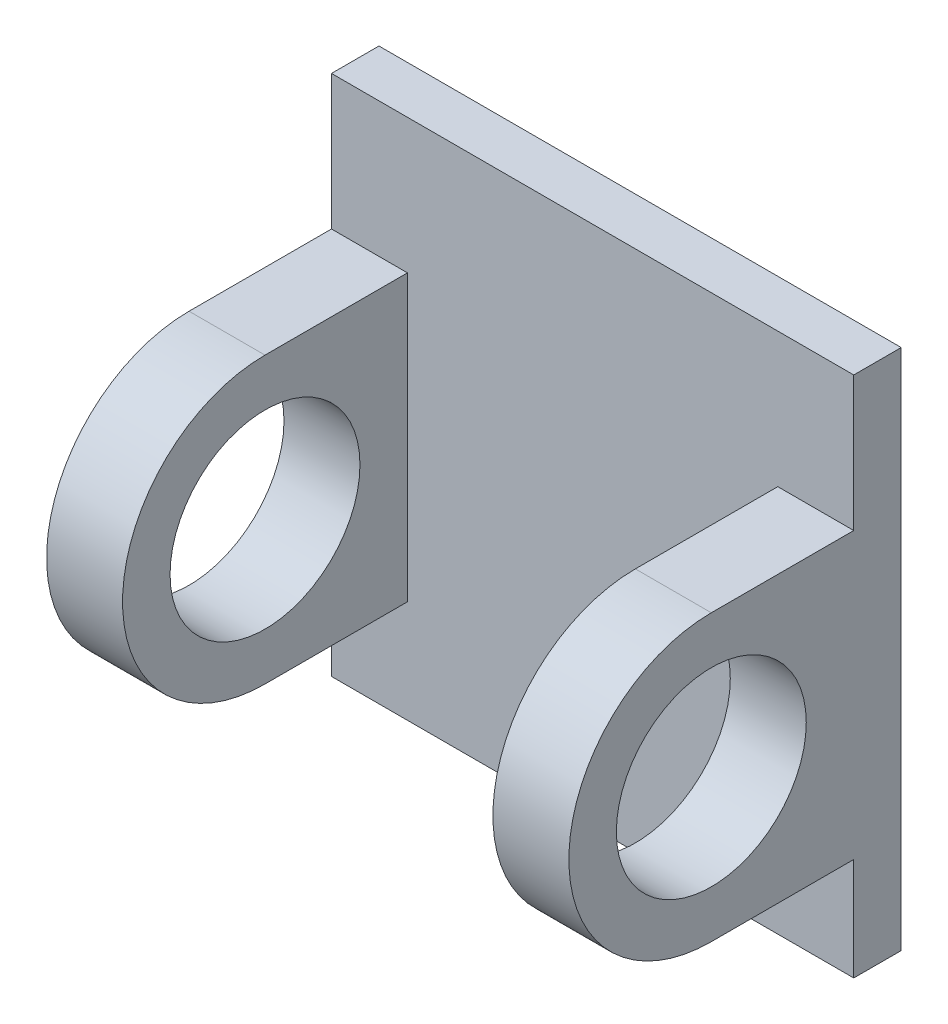
SolidWorks part; units mm, degrees
material "PLA"
ref_plane "Front Plane" through (0, 0, 0) normal (1, 0, 0) x (0, 1, 0)
ref_plane "Top Plane" through (0, 0, 0) normal (0, 0, 1) x (0, 1, 0)
ref_plane "Right Plane" through (0, 0, 0) normal (0, 1, 0) x (-1, 0, 0)
sketch "Sketch1" plane through (0, 0, 0) normal (0, 0, 1) x (0, 1, 0)
  line L1 (-13.75, -13.75) -> (13.75, -13.75)
  line L2 (-13.75, -13.75) -> (-13.75, 13.75)
  line L3 (-13.75, 13.75) -> (13.75, 13.75)
  line L4 (13.75, -13.75) -> (13.75, 13.75)
  line L5 (-13.75, -13.75) -> (13.75, 13.75) construction
  line L6 (-13.75, 13.75) -> (13.75, -13.75) construction
  point P0 (0, 0)
  dimension "D1" = 27.5
extrude "Boss-Extrude1" add sketch "Sketch1" along normal blind 2.5
sketch "Sketch2" plane through (13.75, 0, 0) normal (1, 0, 0) x (0, 1, 0)
  line L0 (-8.3445, 2.5) -> (6.6555, 2.5)
  line L1 (-13.75, 2.5) -> (13.75, 2.5) construction
  line L2 (6.6555, 2.5) -> (6.6555, 10)
  line L3 (-8.3445, 2.5) -> (-8.3445, 10)
  arc A0 (6.6555, 10) -> (-8.3445, 10) centre (-0.8445, 10) ccw
  circle A1 centre (-0.8445, 10) radius 5
  point P5 (-0.8445, 2.5)
  dimension "D1" = 10
  dimension "D2" = 2.5
  dimension "D3" = 7.5
extrude "Boss-Extrude2" add sketch "Sketch2" against normal blind 27.5
sketch "Sketch3" plane through (0, 0, 0) normal (1, 0, 0) x (0, 1, 0)
  line L1 (-13.75, 2.5) -> (13.75, 2.5)
  line L2 (-13.75, 2.5) -> (-13.75, 18.2629)
  line L3 (-13.75, 18.2629) -> (13.75, 18.2629)
  line L4 (13.75, 2.5) -> (13.75, 18.2629)
extrude "Cut-Extrude1" cut sketch "Sketch3" against normal offset from surface 4 and the other way offset from surface 4 up to face at (-13.75, -0.4223, 4.6875) other way up to face at (13.75, -0.4223, 4.6875)
sketch "Sketch4" plane through (0, 13.75, 0) normal (0, 1, 0) x (-1, 0, 0)
  line L1 (-13.75, 0) -> (13.75, 0)
  line L2 (-13.75, 0) -> (-13.75, 2.5)
  line L3 (-13.75, 2.5) -> (13.75, 2.5)
  line L4 (13.75, 0) -> (13.75, 2.5)
extrude "Cut-Extrude2" [suppressed] cut sketch "Sketch4" against normal up to surface (7.0945 mm away) up to face at (11.75, 6.6555, 6.25)
sketch "Sketch5" plane through (0, -13.75, 0) normal (0, -1, 0) x (1, 0, 0)
  line L1 (-13.75, 0) -> (13.75, 0)
  line L2 (-13.75, 0) -> (-13.75, 2.5)
  line L3 (-13.75, 2.5) -> (13.75, 2.5)
  line L4 (13.75, 0) -> (13.75, 2.5)
extrude "Cut-Extrude3" [suppressed] cut sketch "Sketch5" against normal up to surface (5.4055 mm away) up to face at (-11.75, -8.3445, 6.25)
equation "\"ball_diameter\"= 3cm"
equation "\"wall_thickness\" = 0.25cm"
equation "\"track_length\" = 25cm"
equation "\"axle\" = 5mm"
equation "\"pillar_width\" = 2.75cm"
equation "\"D1@Sketch1\"=\"pillar_width\""
equation "\"D1@Boss-Extrude1\"=\"wall_thickness\""
